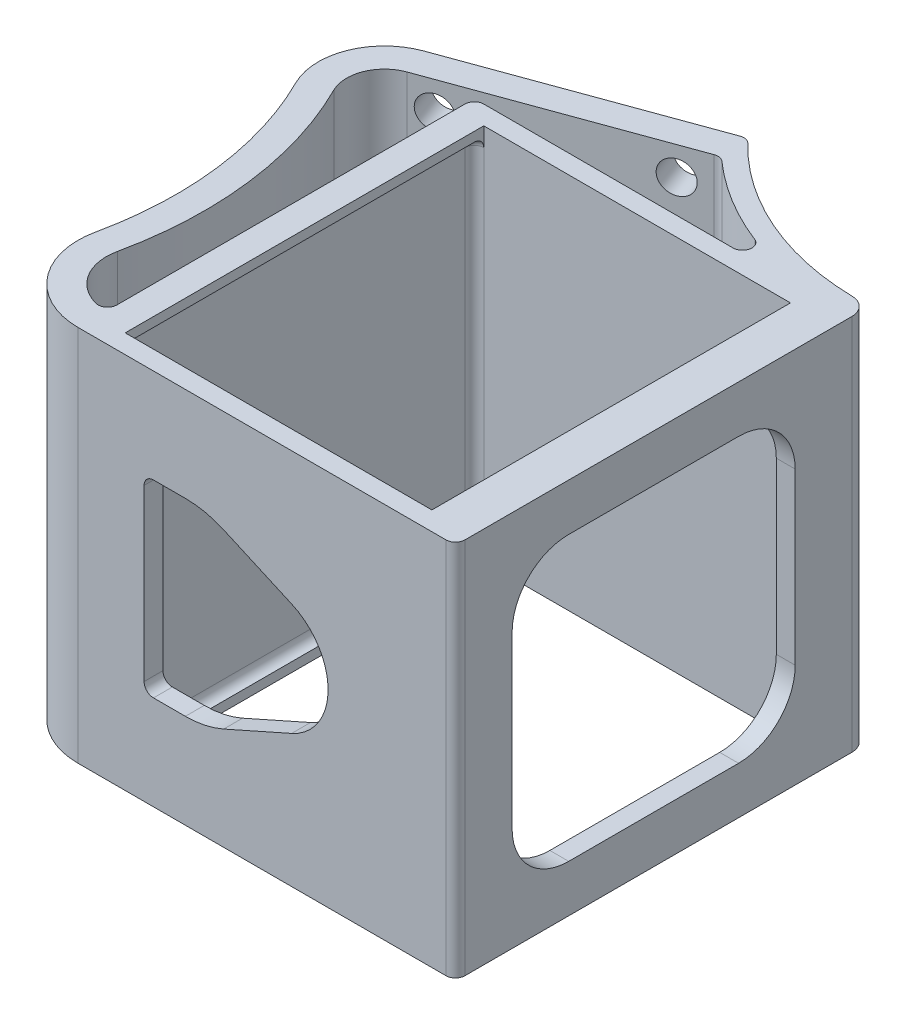
SolidWorks part; units mm, degrees
ref_plane "Draufsicht" through (0, 0, 0) normal (0, 0, 1) x (1, 0, 0)
ref_plane "Seitenansicht" through (0, 0, 0) normal (0, 1, 0) x (1, 0, 0)
ref_plane "Vorderansicht" through (0, 0, 0) normal (1, 0, 0) x (0, 0, -1)
sketch "Skizze1" plane through (0, 0, 0) normal (0, 1, 0) x (1, 0, 0)
  line L1 (-18, 19) -> (18, 19)
  line L2 (-18, 19) -> (-18, -19)
  line L3 (-18, -19) -> (18, -19)
  line L4 (18, 19) -> (18, -19)
  line L6 (18, -19) -> (-18, 19) construction
  line L7 (18, 19) -> (-18, -19) construction
  line L8 (20, -21) -> (20, 21)
  line L9 (20, -21) -> (-20, -21)
  line L10 (16, 21) -> (-20, 21)
  line L11 (-20, 21) -> (-20, -18)
  line L12 (-1.5835, 28.7672) -> (-26.0156, 19.8747)
  line L16 (-1.858, 31.8599) -> (-27.0416, 22.6938)
  arc A0 (-20, -18) -> (-24.8889, -11.9518) centre (-20, -13) cw
  arc A1 (-26.0156, 19.8747) -> (-28.225, 14.3267) centre (-24.6475, 16.1159) ccw
  arc A2 (-28.225, 14.3267) -> (-24.8889, -11.9518) centre (-64, -3.566) cw
  arc A3 (-20, -21) -> (-27.8222, -11.3228) centre (-20, -13) cw
  arc A4 (-27.8222, -11.3228) -> (-30.9081, 12.9847) centre (-64, -3.566) ccw
  arc A5 (-30.9081, 12.9847) -> (-27.0416, 22.6938) centre (-24.6475, 16.1159) cw
  arc A6 (16, 21) -> (-1.5835, 28.7672) centre (18.6912, 50.879) cw
  arc A7 (-1.858, 31.8599) -> (18.1517, 22.8842) centre (18.6912, 50.879) ccw
  arc A8 (18.1517, 22.8842) -> (20, 21) centre (18.1154, 21) cw
  dimension "D10" = 2
  dimension "D13" = 4
  dimension "D14" = 5
  dimension "D15" = 40
  dimension "D16" = 4
  dimension "D17" = 30
  dimension "D1" = 36
  dimension "D2" = 38
  dimension "D3" = 2
  dimension "D4" = 2
  dimension "D5" = 2
  dimension "D6" = 2
  dimension "D7" = 3
  dimension "D8" = 20
  dimension "D9" = 4
  dimension "D11" = 26
  dimension "D12" = 1
extrude "Aufsatz-Linear austragen2" add sketch "Skizze1" along normal blind 40
fillet "Verrundung1" radius 1 5 edges at (20, 20, 21) (16, 20, -21) (-1.5835, 20, -28.7672) (-20, 20, -21) (-20, 20, 18)
sketch "Skizze2" plane through (20, 0, 0) normal (1, 0, 0) x (0, 0, -1)
  line L0 (-19, 1) -> (19, 39) construction
  line L1 (19, 1) -> (-19, 1) construction
  line L3 (19, 39) -> (19, 1) construction
  line L4 (19, 1) -> (-19, 39) construction
  line L5 (-20, 40) -> (-20, 0) construction
  line L8 (-15, 5) -> (15, 5)
  line L9 (-15, 5) -> (-15, 35)
  line L10 (-15, 35) -> (15, 35)
  line L11 (15, 5) -> (15, 35)
  line L12 (19, 39) -> (-19, 39) construction
  line L13 (-19, 39) -> (-19, 1) construction
  line L14 (-20, 20) -> (21, 20) construction
  line L15 (21, 40) -> (21, 0) construction
  line L16 (-19, 20) -> (19, 20) construction
  dimension "D3" = 4
  dimension "D1" = 38
  dimension "D2" = 1
extrude "Schnitt-Linear austragen1" cut sketch "Skizze2" against normal up to next
fillet "Verrundung2" radius 6 4 edges at (19, 35, -15) (19, 35, 15) (19, 5, -15) (19, 5, 15)
hole_wizard "Durchgangsloch für M31" positions "Skizze4" profile "Skizze3" hole size "M3" standard "DIN"
sketch "Skizze4" plane through (-10.4569, 0, -28.7301) normal (-0.342, 0, -0.9397) x (-0.9397, 0, 0.342)
  line L1 (-4.6508, 37) -> (15.3492, 37) construction
  line L2 (-4.6508, 37) -> (-4.6508, 3) construction
  line L3 (-4.6508, 3) -> (15.3492, 3) construction
  line L4 (15.3492, 37) -> (15.3492, 3) construction
  line L5 (-9.1508, 20) -> (17.6491, 20) construction
  line L6 (-9.1508, 40) -> (-9.1508, 0) construction
  line L7 (17.6491, 40) -> (17.6491, 0) construction
  line L9 (-4.6508, 20) -> (15.3492, 20) construction
  point P0 (-4.6508, 37)
  point P2 (15.3492, 3)
  point P4 (-4.6508, 3)
  point P6 (15.3492, 37)
  dimension "D1" = 20
  dimension "D2" = 34
  dimension "D3" = 4.5
sketch "Skizze3" plane through (-6.0866, 37, -30.3208) normal (0, 1, 0) x (-0.9397, 0, 0.342)
  line L0 (0, 0) -> (0, 4.0215)
  line L1 (0, 4.0215) -> (1.7, 3)
  line L2 (1.7, 3) -> (1.7, 0)
  line L5 (1.7, 0) -> (0, 0)
  line L10 (0, 4.0215) -> (-1.7, 3) construction
  line L11 (0, -6.35) -> (0, 107.95) construction
  dimension "Bohrerdurchmesser" = 3.4
  dimension "Bohrungstiefe" = 3
  dimension "Spitzenwinkel" = 118
sketch "Skizze5" plane through (0, 0, 0) normal (0, -1, 0) x (1, 0, 0)
  line L0 (-18, 19) -> (18, 19) construction
  line L1 (15.5, 19) -> (18, 19)
  line L2 (15.5, 19) -> (15.5, -19)
  line L3 (15.5, -19) -> (18, -19)
  line L4 (18, 19) -> (18, -19)
  line L5 (18, 19) -> (18, -19) construction
  line L6 (18, -19) -> (-18, -19) construction
  line L7 (-18, -19) -> (-18, 19) construction
  line L8 (-17, 19) -> (-18, 19)
  line L9 (-17, 19) -> (-17, -19)
  line L10 (-17, -19) -> (-18, -19)
  line L11 (-18, 19) -> (-18, -19)
  dimension "D1" = 2.5
  dimension "D2" = 1
extrude "Aufsatz-Linear austragen3" add sketch "Skizze5" against normal blind 2
sketch "Skizze8" plane through (0, 2, 0) normal (0, 1, 0) x (1, 0, 0)
  line L1 (-17, -19) -> (-18, -19)
  line L2 (-17, -19) -> (-17, 19)
  line L3 (-17, 19) -> (-18, 19)
  line L4 (-18, -19) -> (-18, 19)
extrude "Schnitt-Linear austragen3" cut sketch "Skizze8" against normal blind 1
sketch "Skizze6" plane through (0, 40, 0) normal (0, 1, 0) x (1, 0, 0)
  line L0 (-18, -19) -> (18, -19) construction
  line L1 (15.5, -19) -> (18, -19)
  line L2 (15.5, -19) -> (15.5, 19)
  line L3 (15.5, 19) -> (18, 19)
  line L4 (18, -19) -> (18, 19)
  line L5 (18, -19) -> (18, 19) construction
  line L6 (-18, 19) -> (-18, -19) construction
  line L7 (-17, -19) -> (-18, -19)
  line L8 (-17, -19) -> (-17, 19)
  line L9 (-17, 19) -> (-18, 19)
  line L10 (-18, -19) -> (-18, 19)
  line L11 (18, 19) -> (-18, 19) construction
  dimension "D1" = 1
  dimension "D2" = 2.5
extrude "Aufsatz-Linear austragen4" add sketch "Skizze6" against normal blind 2
sketch "Skizze9" plane through (0, 38, 0) normal (0, -1, 0) x (1, 0, 0)
  line L1 (-17, 19) -> (-18, 19)
  line L2 (-17, 19) -> (-17, -19)
  line L3 (-17, -19) -> (-18, -19)
  line L4 (-18, 19) -> (-18, -19)
extrude "Schnitt-Linear austragen4" cut sketch "Skizze9" against normal blind 1
fillet "Verrundung3" radius 1 12 edges at (18, 38, 0) (18, 20, -19) (18, 2, 0) (18, 20, 19) (-18, 20, -19) (-18, 20, 19) (16.75, 2, -19) (16.75, 2, 19) (16.75, 38, 19) (16.75, 38, -19) (-18, 39, 0) (-18, 1, 0)
fillet "Verrundung4" radius 1 1 edges at (-1.858, 20, -31.8599)
sketch "Skizze7" plane through (0, 0, 21) normal (0, 0, 1) x (1, 0, 0)
  line L0 (-13, 10) -> (-6.5, 10)
  line L1 (-13, 10) -> (-13, 30)
  line L2 (-6.5, 10) -> (2.6388, 14.0598)
  line L3 (-20, 40) -> (-20, 0) construction
  line L4 (19, 20) -> (-20, 20) construction
  line L5 (19, 0) -> (19, 40) construction
  line L6 (-13, 30) -> (-6.5, 30)
  line L7 (-6.5, 30) -> (2.6388, 25.9402)
  arc A0 (2.6388, 25.9402) -> (2.6388, 14.0598) centre (0, 20) cw
  dimension "D5" = 6.5
  dimension "D1" = 7
  dimension "D2" = 20
  dimension "D3" = 19.5
  dimension "D4" = 6.5
extrude "Schnitt-Linear austragen2" cut sketch "Skizze7" against normal up to next
fillet "Verrundung9" radius 1 2 edges at (-13, 30, 20) (-13, 10, 20)
fillet "Verrundung10" radius 10 2 edges at (-6.5, 10, 20) (-6.5, 30, 20)
equation "\"Oberflaeche_cm\"= \"SW-Oberfläche\" / 100"
